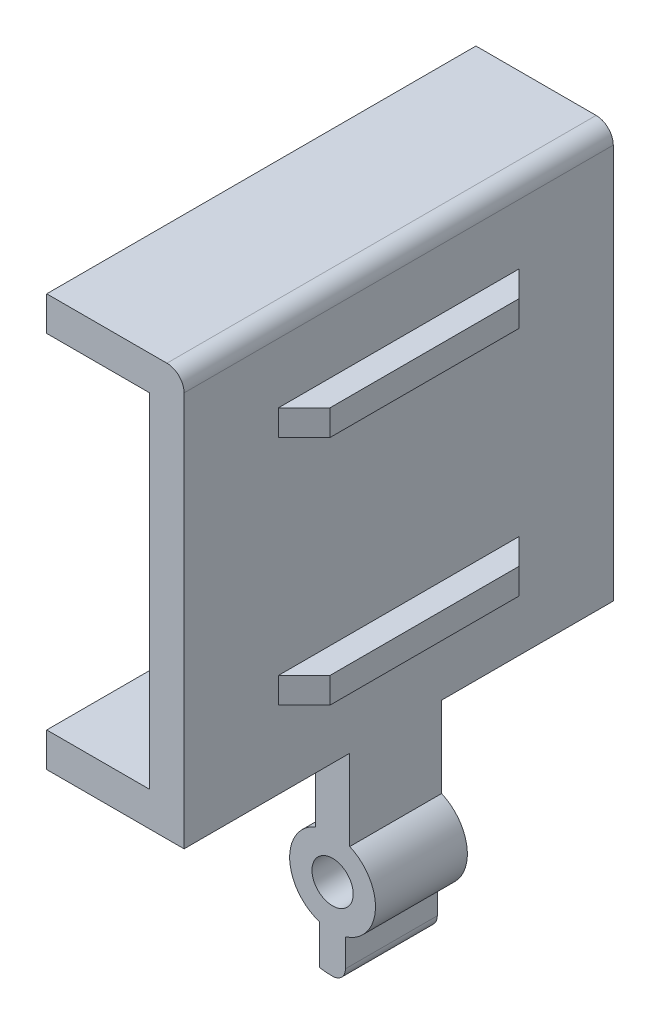
SolidWorks part; units mm, degrees
ref_plane "Front Plane" through (0, 0, 0) normal (0, 0, 1) x (1, 0, 0)
ref_plane "Top Plane" through (0, 0, 0) normal (0, 1, 0) x (1, 0, 0)
ref_plane "Right Plane" through (0, 0, 0) normal (1, 0, 0) x (0, 0, -1)
sketch "housing" plane through (0, 0, 0) normal (0, 0, 1) x (1, 0, 0)
  line L0 (9.2084, 2.3785) -> (7.5875, 5.7496)
  line L1 (0.9916, 2.3785) -> (2.6125, 5.7496)
  line L2 (0.1679, -6.5) -> (3.6321, -6.5)
  line L3 (6.5679, -6.5) -> (10.0321, -6.5)
  line L4 (-0.54, -4.4556) -> (0.9729, 2.3247)
  line L5 (10.74, -4.4556) -> (9.2271, 2.3247)
  line L6 (1.5002, -2.2) -> (2.3931, 1.8019)
  line L7 (2.4305, 1.9096) -> (3.171, 3.4496)
  line L8 (7.7695, 1.9096) -> (7.029, 3.4496)
  line L9 (8.6998, -2.2) -> (7.8069, 1.8019)
  arc A0 (7.5875, 5.7496) -> (2.6125, 5.7496) centre (5.1, 5.5) ccw
  arc A1 (0.9916, 2.3785) -> (0.9729, 2.3247) centre (1.2169, 2.2702) ccw
  arc A2 (9.2271, 2.3247) -> (9.2084, 2.3785) centre (8.9831, 2.2702) ccw
  circle A3 centre (1.9, -5) radius 1
  circle A4 centre (8.3, -5) radius 1
  arc A5 (4.0651, -6.25) -> (1.7584, -2.504) centre (1.9, -5) ccw
  arc A6 (-0.54, -4.4556) -> (-0.2651, -6.25) centre (1.9, -5) ccw
  arc A7 (10.4651, -6.25) -> (10.74, -4.4556) centre (8.3, -5) ccw
  arc A8 (8.4416, -2.504) -> (6.1349, -6.25) centre (8.3, -5) ccw
  arc A9 (-0.2651, -6.25) -> (0.1679, -6.5) centre (0.1679, -6) ccw
  arc A10 (6.1349, -6.25) -> (6.5679, -6.5) centre (6.5679, -6) ccw
  arc A11 (10.0321, -6.5) -> (10.4651, -6.25) centre (10.0321, -6) ccw
  arc A12 (3.6321, -6.5) -> (4.0651, -6.25) centre (3.6321, -6) ccw
  circle A13 centre (5.1, 5.5) radius 1
  arc A14 (3.5512, 3.5376) -> (6.6488, 3.5376) centre (5.1, 5.5) ccw
  arc A15 (2.4305, 1.9096) -> (2.3931, 1.8019) centre (2.8811, 1.693) ccw
  arc A16 (7.8069, 1.8019) -> (7.7695, 1.9096) centre (7.3189, 1.693) ccw
  arc A17 (3.5512, 3.5376) -> (3.171, 3.4496) centre (3.3963, 3.3413) ccw
  arc A18 (7.029, 3.4496) -> (6.6488, 3.5376) centre (6.8037, 3.3413) ccw
  arc A19 (1.5002, -2.2) -> (1.7584, -2.504) centre (1.7442, -2.2544) ccw
  arc A20 (8.4416, -2.504) -> (8.6998, -2.2) centre (8.4558, -2.2544) ccw
sketch "housing_15" plane through (0, 0, 0) normal (0, 0, 1) x (1, 0, 0)
  line L0 (9.2084, 2.3785) -> (7.5875, 5.7496)
  line L1 (0.9916, 2.3785) -> (2.6125, 5.7496)
  line L2 (0.1679, -6.5) -> (3.6321, -6.5)
  line L3 (6.5679, -6.5) -> (10.0321, -6.5)
  line L4 (-0.54, -4.4556) -> (0.9729, 2.3247)
  line L5 (10.74, -4.4556) -> (9.2271, 2.3247)
  line L6 (1.5002, -2.2) -> (2.3931, 1.8019)
  line L7 (2.4305, 1.9096) -> (3.171, 3.4496)
  line L8 (7.7695, 1.9096) -> (7.029, 3.4496)
  line L9 (8.6998, -2.2) -> (7.8069, 1.8019)
  arc A0 (7.5875, 5.7496) -> (2.6125, 5.7496) centre (5.1, 5.5) ccw
  arc A1 (0.9916, 2.3785) -> (0.9729, 2.3247) centre (1.2169, 2.2702) ccw
  arc A2 (9.2271, 2.3247) -> (9.2084, 2.3785) centre (8.9831, 2.2702) ccw
  arc A3 (4.0651, -6.25) -> (1.7584, -2.504) centre (1.9, -5) ccw
  arc A4 (-0.54, -4.4556) -> (-0.2651, -6.25) centre (1.9, -5) ccw
  arc A5 (10.4651, -6.25) -> (10.74, -4.4556) centre (8.3, -5) ccw
  arc A6 (8.4416, -2.504) -> (6.1349, -6.25) centre (8.3, -5) ccw
  arc A7 (-0.2651, -6.25) -> (0.1679, -6.5) centre (0.1679, -6) ccw
  arc A8 (6.1349, -6.25) -> (6.5679, -6.5) centre (6.5679, -6) ccw
  arc A9 (10.0321, -6.5) -> (10.4651, -6.25) centre (10.0321, -6) ccw
  arc A10 (3.6321, -6.5) -> (4.0651, -6.25) centre (3.6321, -6) ccw
  arc A11 (3.5512, 3.5376) -> (6.6488, 3.5376) centre (5.1, 5.5) ccw
  arc A12 (2.4305, 1.9096) -> (2.3931, 1.8019) centre (2.8811, 1.693) ccw
  arc A13 (7.8069, 1.8019) -> (7.7695, 1.9096) centre (7.3189, 1.693) ccw
  arc A14 (3.5512, 3.5376) -> (3.171, 3.4496) centre (3.3963, 3.3413) ccw
  arc A15 (7.029, 3.4496) -> (6.6488, 3.5376) centre (6.8037, 3.3413) ccw
  arc A16 (1.5002, -2.2) -> (1.7584, -2.504) centre (1.7442, -2.2544) ccw
  arc A17 (8.4416, -2.504) -> (8.6998, -2.2) centre (8.4558, -2.2544) ccw
  circle A18 centre (5.1, 5.5) radius 0.75
  circle A19 centre (1.9, -5) radius 0.75
  circle A20 centre (8.3, -5) radius 0.75
sketch "lever" plane through (0, 0, 0) normal (0, 0, 1) x (1, 0, 0)
  line L0 (-0.75, -4.6904) -> (-0.75, -2.3848)
  line L1 (0.75, -4) -> (0.75, -2.3848)
  line L2 (-1, 2.2913) -> (-1, 30)
  line L3 (1, 2.2913) -> (1, 30)
  circle A0 centre (0, 0) radius 1
  arc A1 (-1, 2.2913) -> (-0.75, -2.3848) centre (0, 0) ccw
  arc A2 (0.75, -2.3848) -> (1, 2.2913) centre (0, 0) ccw
  arc A3 (-0.75, -4.6904) -> (0, -4.75) centre (0, 0) ccw
  arc A4 (0, -4.75) -> (0.75, -4) centre (0, -4) ccw
  arc A5 (1, 30) -> (-1, 30) centre (0, 30) ccw
  point P13 (0.75, -3.1924)
  dimension "D1" = 1
  dimension "D2" = 2
  dimension "D3" = 2.5
  dimension "D4" = 2.5
  dimension "D8" = 0.75
  dimension "D5" = 1.5
  dimension "D6" = 30
  dimension "D7" = 4
sketch "mid" plane through (0, 0, 0) normal (0, 0, 1) x (1, 0, 0)
  line L0 (7.7218, 2.0087) -> (7.0755, 3.3529)
  line L1 (2.4782, 2.0087) -> (3.1245, 3.3529)
  line L2 (9.0197, 2.0229) -> (7.9837, 1.8698)
  line L3 (1.1803, 2.0229) -> (2.2163, 1.8698)
  line L4 (9.2084, 2.3785) -> (8.1463, 4.5875)
  line L5 (0.9916, 2.3785) -> (2.0537, 4.5875)
  arc A0 (7.1174, 3.6312) -> (7.6859, 4.5642) centre (5.1, 5.5) ccw
  arc A1 (2.5141, 4.5642) -> (3.0826, 3.6312) centre (5.1, 5.5) ccw
  arc A2 (8.1463, 4.5875) -> (7.6859, 4.5642) centre (7.921, 4.4792) ccw
  arc A3 (2.5141, 4.5642) -> (2.0537, 4.5875) centre (2.279, 4.4792) ccw
  arc A4 (7.1174, 3.6312) -> (7.0755, 3.3529) centre (7.3008, 3.4613) ccw
  arc A5 (3.1245, 3.3529) -> (3.0826, 3.6312) centre (2.8992, 3.4613) ccw
  arc A6 (7.7218, 2.0087) -> (7.9837, 1.8698) centre (7.9471, 2.1171) ccw
  arc A7 (2.2163, 1.8698) -> (2.4782, 2.0087) centre (2.2529, 2.1171) ccw
  arc A8 (9.0197, 2.0229) -> (9.2084, 2.3785) centre (8.9831, 2.2702) ccw
  arc A9 (0.9916, 2.3785) -> (1.1803, 2.0229) centre (1.2169, 2.2702) ccw
extrude "Boss-Extrude1" add sketch "lever" along normal blind 5.35
sketch "Sketch1" plane through (0, 0, 5.35) normal (0, 0, 1) x (1, 0, 0)
  circle A0 centre (0, 0) radius 1.2
  dimension "D1" = 2.4
extrude "Cut-Extrude1" cut sketch "Sketch1" against normal through all
sketch "Sketch2" plane through (0, 0, 5.35) normal (0, 0, 1) x (1, 0, 0)
  circle A0 centre (0, 30) radius 5.5
  dimension "D1" = 11
extrude "Boss-Extrude2" [suppressed] add sketch "Sketch2" against normal through all
sketch "Sketch3" [suppressed] plane through (0, 0, 5.35) normal (0, 0, 1) x (1, 0, 0)
  circle A0 centre (0, 20) radius 4.7625
  dimension "D1" = 9.525
extrude "Cut-Extrude2" [suppressed] cut sketch "Sketch3" against normal through all
pattern_linear "LPattern1" [suppressed] count 3 spacing 10.5 of bodies 104
fillet "Fillet1" [suppressed] radius 0.5
sketch "Sketch4" plane through (0, 0, 0) normal (0, 0, -1) x (-1, 0, 0)
  line L0 (0, 31) -> (7, 31)
  line L1 (7, 31) -> (7, 29)
  line L2 (7, 29) -> (1, 29)
  line L3 (1, 30) -> (1, 2.2913) construction
  line L4 (1, 29) -> (1, 30)
  arc A0 (1, 30) -> (-1, 30) centre (0, 30) ccw construction
  arc A1 (1, 30) -> (0, 31) centre (0, 30) ccw
  dimension "D1" = 2
  dimension "Jaw_height" = 6
extrude "UpperJaw" add sketch "Sketch4" against normal up to surface (5.35 mm away) up to face at (1.2, 0, 5.35)
sketch "Sketch5" plane through (0, 0, 0) normal (0, 0, -1) x (-1, 0, 0)
  line L0 (1, 29) -> (1, 2.2913) construction
  line L1 (1, 7) -> (7, 7)
  line L2 (1, 7) -> (1, 9)
  line L3 (1, 9) -> (7, 9)
  line L4 (7, 7) -> (7, 9)
  line L5 (1, 29) -> (7, 29) construction
  line L6 (7, 29) -> (7, 31) construction
  dimension "2nd_Tang_Dim" = 22
extrude "LowerJaw" add sketch "Sketch5" against normal through all contours L3 L4 L1 L2
sketch "Sketch6" plane through (0, 0, 0) normal (0, 0, -1) x (-1, 0, 0)
  line L0 (-1, 2.2913) -> (-1, 30) construction
  line L1 (-1, 11.5) -> (-2.5, 11.5)
  line L2 (-1, 11.5) -> (-1, 26.5)
  line L3 (-1, 26.5) -> (-2.5, 26.5)
  line L4 (-2.5, 11.5) -> (-2.5, 26.5)
  line L5 (1, 29) -> (1, 9) construction
  point P6 (-1, 19)
  point P9 (1, 19)
  dimension "D1" = 1.5
  dimension "D2" = 15
extrude "BandCapture" add sketch "Sketch6" against normal blind 10 and the other way blind 5
sketch "Sketch7" plane through (0, 0, 0) normal (0, 0, -1) x (-1, 0, 0)
  line L0 (-2.5, 26.5) -> (-2.5, 11.5) construction
  line L1 (-2.5, 25) -> (-1, 25)
  line L2 (-2.5, 25) -> (-2.5, 13)
  line L3 (-2.5, 13) -> (-1, 13)
  line L4 (-1, 25) -> (-1, 13)
  line L5 (-1, 26.5) -> (-2.5, 26.5) construction
  line L6 (-2.5, 11.5) -> (-1, 11.5) construction
  line L7 (-1, 26.5) -> (-1, 30) construction
  dimension "D1" = 1.5
  dimension "D2" = 1.5
extrude "Cut-Extrude3" cut sketch "Sketch7" against normal through all and the other way through all
sketch "Sketch8" plane through (0, 0, 0) normal (0, 0, -1) x (-1, 0, 0)
  line L0 (1, 7) -> (7, 7) construction
  line L1 (7, 7) -> (7, 9) construction
  line L2 (1, 9) -> (7, 9) construction
  line L3 (1, 29) -> (1, 9) construction
  line L4 (-1, 26.5) -> (-1, 30) construction
  line L5 (7, 29) -> (7, 31) construction
  line L6 (1, 29) -> (7, 29) construction
  line L7 (7, 31) -> (0, 31) construction
  line L8 (-1, 7) -> (7, 7)
  line L9 (7, 7) -> (7, 9)
  line L10 (1, 9) -> (7, 9)
  line L11 (1, 29) -> (1, 9)
  line L12 (-1, 7) -> (-1, 30)
  line L13 (7, 29) -> (7, 31)
  line L14 (1, 29) -> (7, 29)
  line L15 (7, 31) -> (0, 31)
  line L16 (-1, 2.2913) -> (-1, 11.5) construction
  arc A0 (0, 31) -> (-1, 30) centre (0, 30) ccw construction
  arc A1 (0, 31) -> (-1, 30) centre (0, 30) ccw
extrude "BatteryCradleWidth" add sketch "Sketch8" along normal blind 10 and the other way blind 15
chamfer "Chamfer1" distance 2 angle 45 4 edges at (2.5, 25.75, 10) (2.5, 12.25, 10) (2.5, 12.25, -5) (2.5, 25.75, -5)
